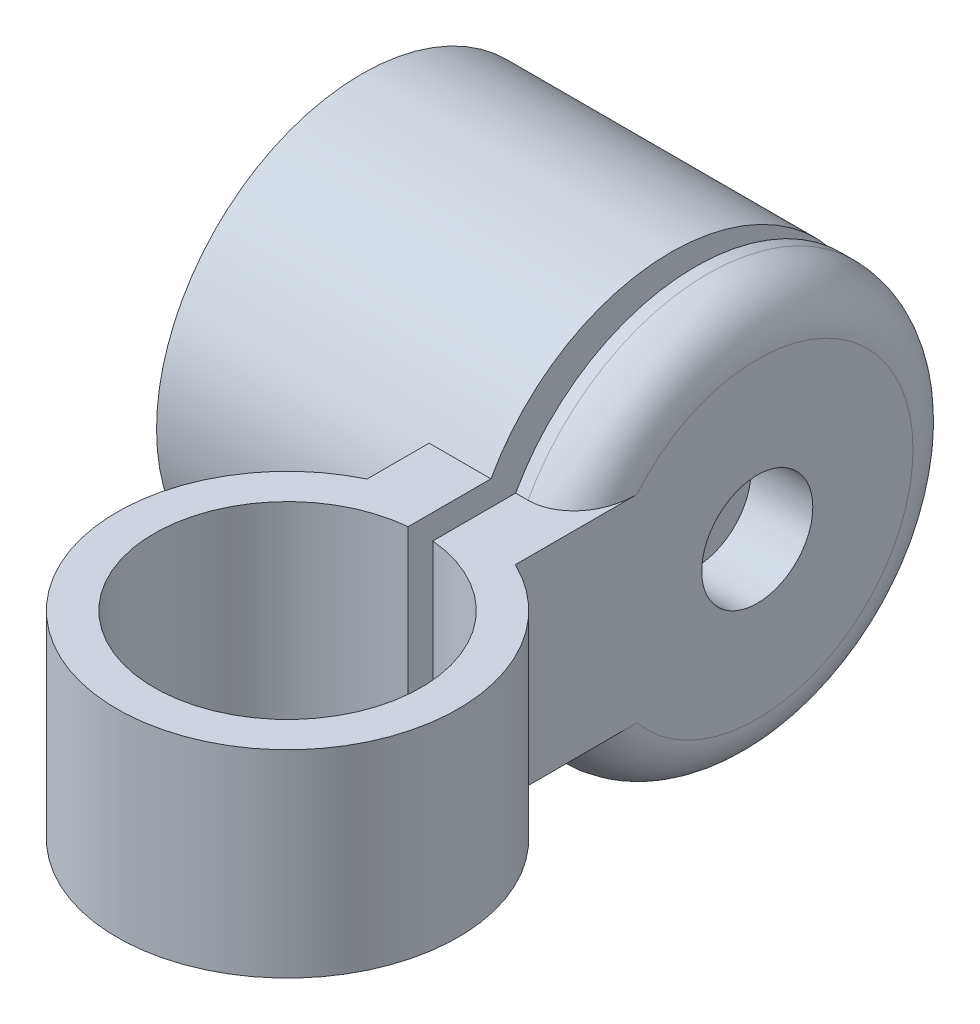
SolidWorks part; units mm, degrees
ref_plane "Front Plane" through (0, 0, 0) normal (0, 0, 1) x (1, 0, 0)
ref_plane "Top Plane" through (0, 0, 0) normal (0, 1, 0) x (1, 0, 0)
ref_plane "Right Plane" through (0, 0, 0) normal (1, 0, 0) x (0, 0, -1)
sketch "Sketch1" plane through (0, 0, 0) normal (0, 1, 0) x (1, 0, 0)
  line L1 (3, -6.2) -> (-3, -6.2)
  line L2 (3, -6.2) -> (3, 20)
  line L3 (3, 20) -> (-3, 20)
  line L4 (-3, -6.2) -> (-3, 20)
  line L5 (3, -6.2) -> (-3, 20) construction
  line L6 (3, 20) -> (-3, -6.2) construction
  line L7 (0.5, -6.2) -> (-0.5, -6.2)
  line L8 (0.5, -6.2) -> (0.5, 20)
  line L9 (0.5, 20) -> (-0.5, 20)
  line L10 (-0.5, -6.2) -> (-0.5, 20)
  line L11 (0.5, -6.2) -> (-0.5, 20) construction
  line L12 (0.5, 20) -> (-0.5, -6.2) construction
  circle A0 centre (0, 0) radius 5.4
  circle A1 centre (0, 0) radius 6.9
  point P4 (0, 6.9)
  point P9 (0, 6.9)
  dimension "D1" = 10.8
  dimension "D2" = 1.5
  dimension "D3" = 6
  dimension "D4" = 20
  dimension "D5" = 1
extrude "Boss-Extrude1" add sketch "Sketch1" along normal blind 8 contours L4 A1 L2 A0 | L10 A1 L4 A0 | A1 L10 L3 L4 | A1 L2 L3 L8 | L2 A1 L8 A0 | A0 L4 L1 L10 | A0 L8 L1 L2 | A0 L10 L1 L8 region at (3.1904, 0, 5.345) region at (1.9085, 0, 5.5965) region at (0, 0, 5.7961) region at (-1.9085, 0, 5.5965) region at (1.7778, 0, -5.8326) region at (1.7603, 0, -13.3148) region at (-1.7778, 0, -5.8326) region at (-1.7603, 0, -13.3148)
sketch "Sketch2" plane through (3, 0, 0) normal (1, 0, 0) x (0, 0, -1)
  line L1 (20, 8) -> (20, 0) construction
  line L2 (20, 8) -> (20, 0) construction
  point P0 (16, 4)
  point P6 (20, 4)
  dimension "D1" = 4
  dimension "D2" = 0
hole_wizard "#8 Clearance Hole1" positions "Sketch3" profile "Sketch4" hole size "#8" standard "ANSI Inch" end condition through all
sketch "Sketch3" plane through (3, 0, 0) normal (1, 0, 0) x (0, 0, -1)
  point P0 (16, 4)
sketch "Sketch4" plane through (3, 4, -16) normal (0, 1, 0) x (0, 0, -1)
  line L0 (0, 0) -> (0, 9.9)
  line L1 (0, 9.9) -> (2.2479, 9.9)
  line L2 (2.2479, 9.9) -> (2.2479, 0)
  line L5 (2.2479, 0) -> (0, 0)
  line L11 (0, -6.35) -> (0, 107.95) construction
  dimension "Thru Hole Dia." = 4.4958
  dimension "Thru Hole Depth" = 9.9
sketch "Sketch5" plane through (-3, 0, 0) normal (-1, 0, 0) x (0, 0, 1)
  circle A0 centre (-16, 4) radius 6.3
  circle A1 centre (-16, 4) radius 8.3
  dimension "D1" = 12.6
  dimension "D2" = 2
extrude "Boss-Extrude2" add sketch "Sketch5" along normal blind 10
sketch "Sketch6" plane through (-0.5, 0, 0) normal (1, 0, 0) x (0, 0, -1)
  arc A2 (8.7274, 0) -> (8.7274, 8) centre (16, 4) ccw
  arc A3 (8.7274, 0) -> (8.7274, 8) centre (16, 4) ccw
  circle A5 centre (16, 4) radius 2.2479
  circle A6 centre (16, 4) radius 2.2479
  line M4 (5.3768, 0) -> (20, 0)
  line M5 (20, 0) -> (20, 8)
  line M6 (20, 8) -> (5.3768, 8)
  dimension "D1" = 0
  dimension "D2" = 0
extrude "Boss-Extrude3" add sketch "Sketch6" against normal up to surface (2.5 mm away) contours A3 M4 M6 M5 region at (-0.5, -0.2276, -14.3637) up to face at (-3, 4, -16.6151)
extrude "Boss-Extrude4" add sketch "Sketch6<4>" along normal up to surface (3.5 mm away) from surface contours A3 M4 M6 M5 region at (-0.5, -0.2276, -14.3637) up to face at (3, 4, -18.2479) starting at face at (0.5, 4, -13.7521)
sketch "Sketch6<4>" plane through (-0.5, 0, 0) normal (1, 0, 0) x (0, 0, -1) same geometry as "Sketch6"
fillet "Fillet1" radius 2 1 edges at (3, 4, -24.3)
chamfer "Chamfer1" distance 1 angle 60 1 edges at (-3, 4, -9.7) first distance on face at (-3, 4, -13.7521)
